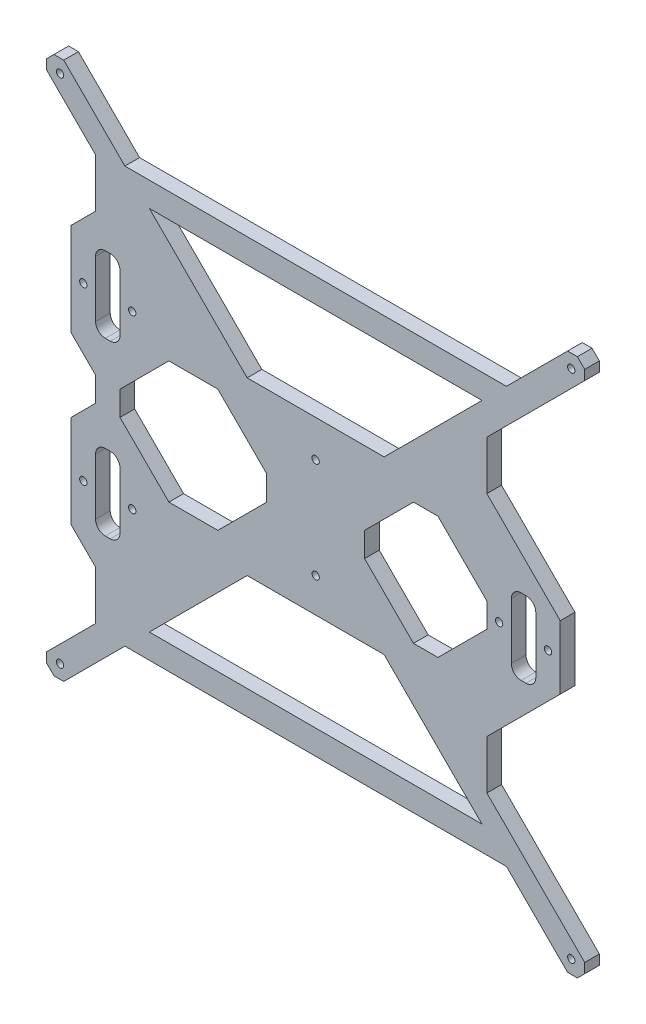
SolidWorks part; units mm, degrees
ref_plane "Plano frontal" through (0, 0, 0) normal (0, 0, 1) x (1, 0, 0)
ref_plane "Plano superior" through (0, 0, 0) normal (0, 1, 0) x (1, 0, 0)
ref_plane "Plano direito" through (0, 0, 0) normal (1, 0, 0) x (0, 0, -1)
sketch "Model" plane through (0, 0, 0) normal (0, 0, 1) x (1, 0, 0)
  line L0 (27.2239, 227.8488) -> (25.2239, 227.8488)
  line L1 (25.2239, 227.8488) -> (22.2239, 224.8488)
  line L2 (22.2239, 224.8488) -> (22.2239, 222.8488)
  line L3 (22.2239, 222.8488) -> (22.2239, 220.8488)
  line L4 (22.2239, 220.8488) -> (42.2239, 200.8488)
  line L5 (42.2239, 200.8488) -> (42.2239, 180.8488)
  line L6 (42.2239, 180.8488) -> (32.2239, 170.8488)
  line L7 (32.2239, 64.8488) -> (42.2239, 54.8488)
  line L8 (22.2239, 14.8488) -> (42.2239, 34.8488)
  line L9 (42.2239, 34.8488) -> (42.2239, 54.8488)
  line L10 (22.2239, 14.8488) -> (22.2239, 10.8488)
  line L11 (22.2239, 10.8488) -> (25.2239, 7.8488)
  line L12 (25.2239, 7.8488) -> (27.2239, 7.8488)
  line L13 (237.2239, 7.8488) -> (239.2239, 7.8488)
  line L14 (239.2239, 7.8488) -> (242.2239, 10.8488)
  line L15 (242.2239, 223.8488) -> (242.2239, 224.8488)
  line L16 (242.2239, 224.8488) -> (239.2239, 227.8488)
  line L17 (242.2239, 220.8488) -> (202.2239, 180.8488)
  line L18 (232.2239, 130.8488) -> (222.2239, 140.8488)
  line L19 (222.2239, 140.8488) -> (202.2239, 160.8488)
  line L20 (202.2239, 160.8488) -> (202.2239, 180.8488)
  line L21 (232.2239, 104.8488) -> (222.2239, 94.8488)
  line L22 (222.2239, 94.8488) -> (202.2239, 74.8488)
  line L23 (242.2239, 14.8488) -> (222.2239, 34.8488)
  line L24 (222.2239, 34.8488) -> (202.2239, 54.8488)
  line L25 (202.2239, 54.8488) -> (202.2239, 74.8488)
  line L26 (235.2239, 227.8488) -> (212.2239, 204.8488)
  line L27 (172.2239, 164.8488) -> (170.2239, 162.8488)
  line L28 (170.2239, 162.8488) -> (160.2239, 152.8488)
  line L29 (160.2239, 152.8488) -> (104.2239, 152.8488)
  line L30 (235.2239, 7.8488) -> (210.2239, 32.8488)
  line L31 (160.2239, 82.8488) -> (104.2239, 82.8488)
  line L32 (54.2239, 202.8488) -> (210.2239, 202.8488)
  line L33 (54.2239, 32.8488) -> (210.2239, 32.8488)
  line L34 (32.2239, 132.8488) -> (42.2239, 122.8488)
  line L35 (42.2239, 122.8488) -> (42.2239, 112.8488)
  line L36 (42.2239, 112.8488) -> (32.2239, 102.8488)
  line L37 (52.2239, 122.8488) -> (72.2239, 142.8488)
  line L38 (72.2239, 142.8488) -> (92.2239, 142.8488)
  line L39 (92.2239, 142.8488) -> (112.2239, 122.8488)
  line L40 (112.2239, 122.8488) -> (112.2239, 112.8488)
  line L41 (112.2239, 112.8488) -> (92.2239, 92.8488)
  line L42 (92.2239, 92.8488) -> (72.2239, 92.8488)
  line L43 (72.2239, 92.8488) -> (52.2239, 112.8488)
  line L44 (52.2239, 112.8488) -> (52.2239, 122.8488)
  line L45 (182.2239, 142.8488) -> (202.2239, 122.8488)
  line L46 (202.2239, 122.8488) -> (202.2239, 112.8488)
  line L47 (202.2239, 112.8488) -> (182.2239, 92.8488)
  line L48 (182.2239, 92.8488) -> (172.2239, 92.8488)
  line L49 (172.2239, 92.8488) -> (152.2239, 112.8488)
  line L50 (152.2239, 112.8488) -> (152.2239, 122.8488)
  line L51 (152.2239, 122.8488) -> (172.2239, 142.8488)
  line L52 (172.2239, 142.8488) -> (182.2239, 142.8488)
  line L53 (27.2239, 227.8488) -> (29.2239, 227.8488)
  line L54 (239.2239, 227.8488) -> (235.2239, 227.8488)
  line L55 (242.2239, 223.8488) -> (242.2239, 220.8488)
  line L56 (242.2239, 14.8488) -> (242.2239, 10.8488)
  line L57 (235.2239, 7.8488) -> (237.2239, 7.8488)
  line L58 (29.2239, 7.8488) -> (27.2239, 7.8488)
  line L59 (64.2239, 192.8488) -> (200.2239, 192.8488)
  line L60 (212.2239, 204.8488) -> (210.2239, 202.8488)
  line L61 (200.2239, 192.8488) -> (172.2239, 164.8488)
  line L62 (29.2239, 227.8488) -> (54.2239, 202.8488)
  line L63 (64.2239, 192.8488) -> (104.2239, 152.8488)
  line L64 (200.2239, 42.8488) -> (64.2239, 42.8488)
  line L65 (29.2239, 7.8488) -> (54.2239, 32.8488)
  line L66 (104.2239, 82.8488) -> (64.2239, 42.8488)
  line L67 (160.2239, 82.8488) -> (200.2239, 42.8488)
  line L68 (32.2239, 170.8488) -> (32.2239, 132.8488)
  line L69 (32.2239, 102.8488) -> (32.2239, 64.8488)
  line L70 (232.2239, 130.8488) -> (232.2239, 104.8488)
  line L71 (42.2239, 71.8488) -> (42.2239, 94.8488)
  line L72 (46.2239, 98.8488) -> (48.2239, 98.8488)
  line L73 (52.2239, 94.8488) -> (52.2239, 71.8488)
  line L74 (48.2239, 67.8488) -> (46.2239, 67.8488)
  line L75 (42.2239, 141.8558) -> (42.2239, 164.8558)
  line L76 (46.2239, 168.8558) -> (48.2239, 168.8558)
  line L77 (52.2239, 164.8558) -> (52.2239, 141.8558)
  line L78 (48.2239, 137.8558) -> (46.2239, 137.8558)
  line L79 (212.2239, 105.7117) -> (212.2239, 128.7117)
  line L80 (216.2239, 132.7117) -> (218.2239, 132.7117)
  line L81 (222.2239, 128.7117) -> (222.2239, 105.7117)
  line L82 (218.2239, 101.7117) -> (216.2239, 101.7117)
  circle A0 centre (37.2239, 152.8488) radius 1.5
  circle A1 centre (57.2239, 152.8488) radius 1.5
  circle A2 centre (37.2239, 82.8488) radius 1.5
  circle A3 centre (57.2239, 82.8488) radius 1.5
  circle A4 centre (227.2239, 117.8488) radius 1.5
  circle A5 centre (207.2239, 117.8488) radius 1.5
  circle A6 centre (27.7239, 222.3488) radius 1.5
  circle A7 centre (236.7239, 13.3488) radius 1.5
  circle A8 centre (236.7239, 222.3488) radius 1.5
  circle A9 centre (27.7239, 13.3488) radius 1.5
  arc A10 (46.2239, 98.8488) -> (42.2239, 94.8488) centre (46.2239, 94.8488) ccw
  arc A11 (52.2239, 94.8488) -> (48.2239, 98.8488) centre (48.2239, 94.8488) ccw
  arc A12 (42.2239, 71.8488) -> (46.2239, 67.8488) centre (46.2239, 71.8488) ccw
  arc A13 (48.2239, 67.8488) -> (52.2239, 71.8488) centre (48.2239, 71.8488) ccw
  circle A14 centre (132.2239, 96.8488) radius 1.5
  circle A15 centre (132.2239, 137.8488) radius 1.5
  arc A16 (48.2239, 137.8558) -> (52.2239, 141.8558) centre (48.2239, 141.8558) ccw
  arc A17 (46.2239, 168.8558) -> (42.2239, 164.8558) centre (46.2239, 164.8558) ccw
  arc A18 (52.2239, 164.8558) -> (48.2239, 168.8558) centre (48.2239, 164.8558) ccw
  arc A19 (42.2239, 141.8558) -> (46.2239, 137.8558) centre (46.2239, 141.8558) ccw
  arc A20 (218.2239, 101.7117) -> (222.2239, 105.7117) centre (218.2239, 105.7117) ccw
  arc A21 (216.2239, 132.7117) -> (212.2239, 128.7117) centre (216.2239, 128.7117) ccw
  arc A22 (222.2239, 128.7117) -> (218.2239, 132.7117) centre (218.2239, 128.7117) ccw
  arc A23 (212.2239, 105.7117) -> (216.2239, 101.7117) centre (216.2239, 105.7117) ccw
extrude "Ressalto-extrusão1" add sketch "Model" along normal blind 6
ref_axis "Eixo1" through (132.2239, 137.8488, 6) along (0, 0, -1)
ref_axis "Eixo2" through (132.2239, 96.8488, 6) along (0, 0, -1)
ref_plane "Plano1" through (132.2239, 0, 0) normal (1, 0, 0) x (0, 0, -1)
ref_plane "Plano2" through (0, 137.8488, 0) normal (0, 1, 0) x (1, 0, 0)
ref_plane "Plano3" through (0, 96.8488, 0) normal (0, -1, 0) x (-1, 0, 0)
ref_plane "Plano4" through (0, 117.3488, 0) normal (0, 1, 0) x (1, 0, 0)
ref_axis "Eixo3" through (27.7239, 222.3488, 6) along (0, 0, -1)
ref_axis "Eixo4" through (236.7239, 222.3488, 6) along (0, 0, -1)
ref_axis "Eixo5" through (236.7239, 13.3488, 6) along (0, 0, -1)
ref_axis "Eixo6" through (27.7239, 13.3488, 6) along (0, 0, -1)
ref_plane "Plano5" through (27.7239, 0, 0) normal (1, 0, 0) x (0, 0, -1)
ref_plane "Plano6" through (0, 222.3488, 0) normal (0, -1, 0) x (-1, 0, 0)
ref_plane "Plano7" through (236.7239, 0, 0) normal (-1, 0, 0) x (0, 0, 1)
ref_plane "Plano8" through (0, 13.3488, 0) normal (0, 1, 0) x (1, 0, 0)
ref_plane "Plano9" through (0, 117.8488, 0) normal (0, 1, 0) x (1, 0, 0)
ref_plane "Plano10" through (132.2239, 0, 0) normal (1, 0, 0) x (0, 0, -1)
ref_plane "Plano11" through (0, 117.2117, 0) normal (0, 1, 0) x (1, 0, 0)
ref_plane "Plano12" through (0, 153.3558, 0) normal (0, -1, 0) x (-1, 0, 0)
ref_plane "Plano13" through (0, 83.3488, 0) normal (0, 1, 0) x (1, 0, 0)
